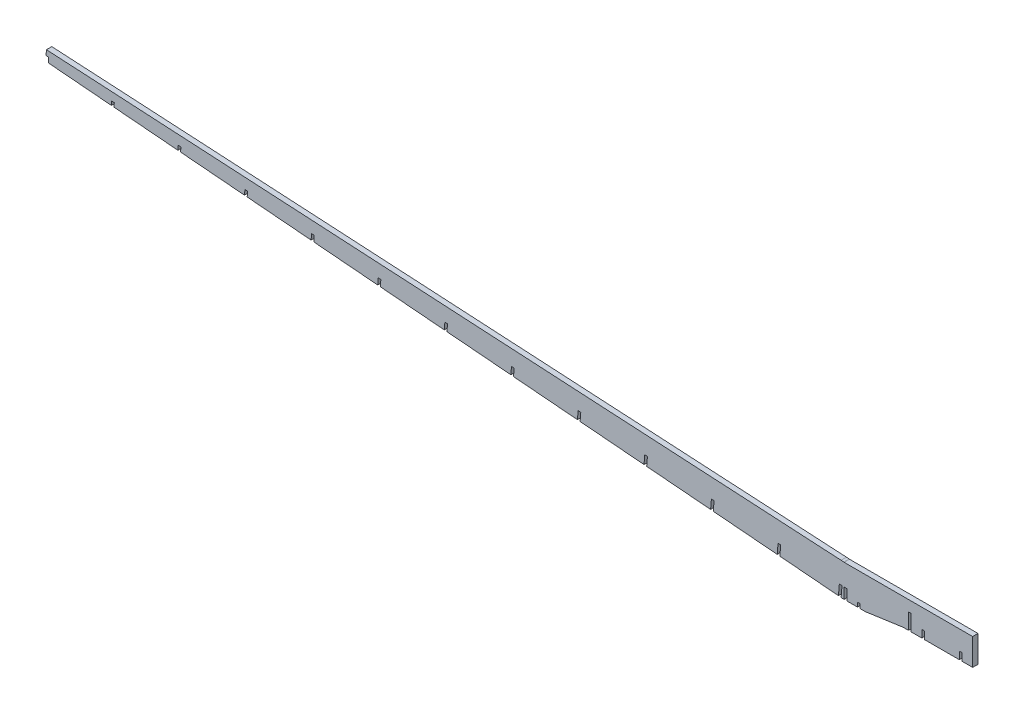
SolidWorks part; units mm, degrees
material "Balsa"
ref_plane "Front Plane" through (0, 0, 0) normal (0, 0, 1) x (1, 0, 0)
ref_plane "Top Plane" through (0, 0, 0) normal (0, 1, 0) x (1, 0, 0)
ref_plane "Right Plane" through (0, 0, 0) normal (1, 0, 0) x (0, 0, -1)
sketch "Sketch1" plane through (0, 0, 0) normal (0, 0, 1) x (1, 0, 0)
  line L0 (76.2, 56.7475) -> (76.2, 37.6975)
  line L1 (79.375, 56.7475) -> (79.375, 37.6975)
  line L2 (0, 44.0475) -> (0, 31.3475)
  line L3 (3.175, 44.0475) -> (3.175, 31.3475)
  line L4 (-5.7133, 44.4467) -> (-6.776, 31.7912)
  line L5 (-2.5494, 44.181) -> (-3.6121, 31.5255)
  line L6 (-1.4923, 31.3475) -> (25.4, 31.3475)
  line L7 (25.4, 31.3475) -> (69.85, 37.6975)
  line L8 (-2.5494, 44.181) -> (-0.424, 69.4919) construction
  line L9 (-0.424, 69.4919) -> (-3.5879, 69.7576)
  line L10 (-3.5879, 69.7576) -> (-5.7133, 44.4467) construction
  line L11 (-5.7133, 44.4467) -> (-2.5494, 44.181)
  line L12 (3.175, 44.0475) -> (3.175, 69.4475) construction
  line L13 (3.175, 69.4475) -> (0, 69.4475)
  line L14 (0, 69.4475) -> (0, 44.0475) construction
  line L15 (0, 44.0475) -> (3.175, 44.0475)
  line L16 (92.075, 37.6975) -> (92.075, 46.5875)
  line L17 (-942.8808, 122.7744) -> (-947.5199, 67.5279)
  line L18 (0, 69.4475) -> (-0.424, 69.4919)
  line L19 (3.175, 69.4475) -> (152.4, 69.4475)
  line L20 (152.4, 69.4475) -> (152.4, 37.6975)
  line L21 (152.4, 37.6975) -> (69.85, 37.6975)
  line L22 (92.075, 46.5875) -> (95.25, 46.5875)
  line L23 (95.25, 46.5875) -> (95.25, 37.6975)
  line L24 (-1.4923, 31.3475) -> (-943.9128, 110.4848)
  line L25 (79.375, 69.4475) -> (79.375, 56.7475)
  line L26 (-942.8808, 122.7744) -> (-3.5879, 69.7576)
  line L27 (136.525, 37.6975) -> (136.525, 46.5875)
  line L28 (76.2, 69.4475) -> (76.2, 56.7475)
  line L29 (79.375, 56.7475) -> (76.2, 56.7475)
  line L30 (-943.5688, 114.5813) -> (-5.7133, 44.4467)
  line L31 (136.525, 46.5875) -> (139.7, 46.5875)
  line L32 (139.7, 46.5875) -> (139.7, 37.6975)
  line L33 (15.875, 31.3475) -> (15.875, 36.4275)
  line L34 (15.875, 36.4275) -> (19.05, 36.4275)
  line L35 (19.05, 36.4275) -> (19.05, 31.3475)
  line L36 (-942.8808, 122.7744) -> (-946.0519, 122.9534)
  line L37 (-946.0519, 122.9534) -> (-946.5835, 116.6233)
  line L38 (-946.5835, 116.6233) -> (-943.4123, 116.4443)
  dimension "D3" = 76.2
  dimension "D10" = 12.3329
  dimension "D11" = 8.2219
  dimension "D2" = 25.4
  dimension "D4" = 25.4
  dimension "D5" = 12.7
  dimension "D7" = 3.175
  dimension "D9" = 3.175
  dimension "D12" = 3.175
  dimension "D6" = 19.05
  dimension "D13" = 6.35
  dimension "D14" = 12.7
  dimension "D16" = 3.175
  dimension "D17" = 3.175
  dimension "D18" = 12.7
  dimension "D19" = 12.7
  dimension "D20" = 8.89
  dimension "D21" = 8.89
  dimension "D15" = 76.2
  dimension "D22" = 12.7
  dimension "D23" = 3.175
  dimension "D24" = 5.08
  dimension "D8" = 6.35
  dimension "D25" = 3.175
  dimension "D26" = 6.35
extrude "Boss-Extrude1" add sketch "Sketch1" along normal mid plane 6.35 contours L17 L30 L11 L5 L24 L6 L2 L15 L3 L7 L21 L0 L28 L19 L13 L18 L9 L26 | L30 L17 L24 L4 | L29 L25 L19 L28 | L19 L25 L1 L21 L20 | L37 L38 L17 L36 region at (-328.9931, 77.9728, 0) region at (77.7875, 63.0975, 0) region at (115.8875, 53.8578, 0) region at (-944.7321, 119.6988, 0) region at (-395.1618, 68.9894, 0)
sketch "Sketch2" plane through (0, 0, 3.175) normal (0, 0, 1) x (1, 0, 0)
  line L2 (-73.2652, 73.2231) -> (-80.3969, -11.7061)
  line L3 (-943.5688, 114.5813) -> (-5.7133, 44.4467)
  line L6 (-76.4291, 73.4888) -> (-83.5608, -11.4404)
  line L7 (-6.776, 31.7912) -> (-943.9128, 110.4848)
  line L10 (-152.4177, 77.6821) -> (-159.3225, -4.5442)
  line L14 (-155.5816, 77.9478) -> (-162.4863, -4.2785)
  line L18 (-231.5658, 82.1932) -> (-238.251, 2.5812)
  line L22 (-234.7297, 82.4589) -> (-241.4149, 2.8469)
  line L26 (-310.7178, 86.6582) -> (-317.1769, 9.7387)
  line L30 (-313.8817, 86.9239) -> (-320.3408, 10.0043)
  line L34 (-389.8657, 91.1713) -> (-396.1056, 16.8623)
  line L38 (-393.0296, 91.437) -> (-399.2695, 17.128)
  line L42 (-469.0186, 95.6263) -> (-475.031, 24.0265)
  line L46 (-472.1824, 95.892) -> (-478.1948, 24.2921)
  line L50 (-548.1666, 100.1381) -> (-553.9596, 31.1506)
  line L54 (-551.3305, 100.4038) -> (-557.1235, 31.4163)
  line L58 (-627.3195, 104.5918) -> (-632.8849, 38.3152)
  line L62 (-630.4834, 104.8575) -> (-636.0488, 38.5809)
  line L66 (-706.4673, 109.1069) -> (-711.8138, 45.4365)
  line L70 (-709.6312, 109.3725) -> (-714.9777, 45.7022)
  line L74 (-785.6206, 113.5558) -> (-790.7389, 52.6041)
  line L78 (-788.7845, 113.8214) -> (-793.9027, 52.8697)
  line L82 (-864.7684, 118.071) -> (-869.6679, 59.7246)
  line L86 (-867.9323, 118.3366) -> (-872.8317, 59.9902)
  line L89 (-942.9091, 122.4365) -> (-947.5795, 66.8182)
  line M2 (-943.9128, 110.4848) -> (-6.776, 31.7912)
extrude "Cut-Extrude1" cut sketch "Sketch2" against normal through all contours L3 L6 L2 M2 | L3 L14 L7 L10 | L3 L22 L7 L18 | L3 L30 L7 L26 | L3 L38 L7 L34 | L3 L46 L7 L42 | L3 L54 L7 L50 | L3 L62 L7 L58 | L3 L70 L7 L66 | L3 L78 L7 L74 | L3 L86 L7 L82 region at (-77.3317, 43.7615, 3.175) region at (-156.332, 50.0322, 3.175) region at (-235.3323, 56.3029, 3.175) region at (-314.3326, 62.5736, 3.175) region at (-393.3328, 68.8442, 3.175) region at (-472.3331, 75.1149, 3.175) region at (-551.3334, 81.3856, 3.175) region at (-630.3336, 87.6563, 3.175) region at (-709.3339, 93.9269, 3.175) region at (-788.334, 100.1976, 3.175) region at (-867.3342, 106.4683, 3.175)
move or copy body "Body-Move/Copy1" [suppressed] bodies to move or copy 102 parameters "D1"=0, "D2"=0, "D3"=0
equation "\"D11@Sketch1\"=\"D10@Sketch1\"*(2/3)"
